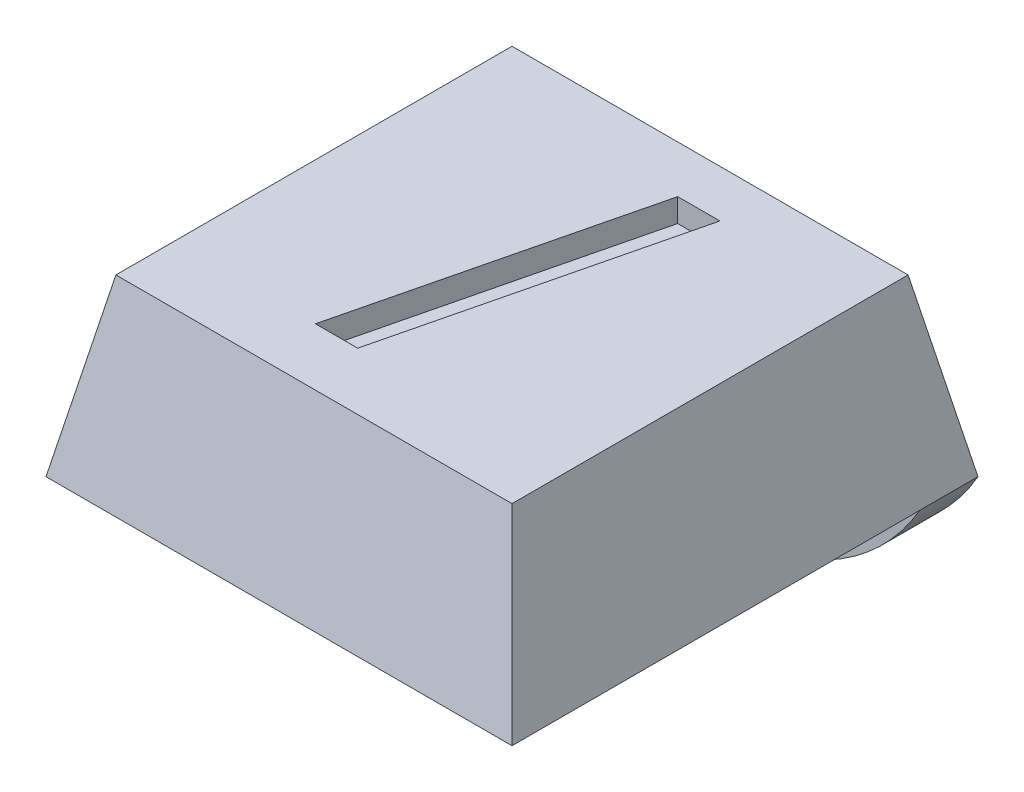
SolidWorks part; units mm, degrees
ref_plane "Front Plane" through (0, 0, 0) normal (0, 0, 1) x (1, 0, 0)
ref_plane "Top Plane" through (0, 0, 0) normal (0, 1, 0) x (1, 0, 0)
ref_plane "Right Plane" through (0, 0, 0) normal (1, 0, 0) x (0, 0, -1)
sketch "Sketch1" plane through (0, 0, 0) normal (0, 1, 0) x (1, 0, 0)
  line L1 (0, 0) -> (8, 0)
  line L2 (0, 0) -> (0, 8)
  line L3 (0, 8) -> (8, 8)
  line L4 (8, 0) -> (8, 8)
  dimension "D1" = 8
  dimension "D2" = 8
extrude "Boss-Extrude1" add sketch "Sketch1" along normal blind 3
sketch "Sketch2" plane through (0, 0, 0) normal (0, 0, 1) x (1, 0, 0)
  line L0 (0, 0) -> (0.6, 3)
  line L1 (0, 3) -> (8, 3) construction
  line L2 (0.6, 3) -> (0, 3)
  line L3 (0, 3) -> (0, 0)
  line L4 (8, 0) -> (7.4, 3)
  line L5 (7.4, 3) -> (8, 3)
  line L6 (8, 3) -> (8, 0)
  dimension "D1" = 0.6
  dimension "D2" = 0.6
extrude "Cut-Extrude1" cut sketch "Sketch2" against normal through all both and the other way through all
sketch "Sketch3" plane through (0, 0, 0) normal (1, 0, 0) x (0, 0, -1)
  line L0 (0, 0) -> (0.6, 3)
  line L1 (8, 3) -> (0, 3) construction
  line L2 (0.6, 3) -> (0, 3)
  line L3 (0, 3) -> (0, 0)
  line L4 (8, 3) -> (7.4, 3)
  line L5 (7.4, 3) -> (8, 0)
  line L6 (8, 3) -> (8, 0)
  dimension "D1" = 0.6
  dimension "D2" = 0.6
extrude "Cut-Extrude2" cut sketch "Sketch3" along normal blind 11
sketch "Sketch4" plane through (0, 0, 0) normal (0, -1, 0) x (1, 0, 0)
  line L0 (8, 0) -> (8, -8) construction
  line L3 (0, 0) -> (8, 0) construction
  circle A0 centre (4, -3.75) radius 1.75
  dimension "D1" = 3.5
  dimension "D2" = 4
  dimension "D3" = 3.75
extrude "Cut-Extrude3" cut sketch "Sketch4" against normal blind 0.4
sketch "Sketch5" plane through (0, 0, 0) normal (0, -1, 0) x (1, 0, 0)
  line L0 (8, 0) -> (8, -8) construction
  line L1 (0, -8) -> (8, -8)
  line L2 (0, -8) -> (0, -7)
  line L3 (0, -7) -> (8, -7)
  line L4 (8, -8) -> (8, -7)
  dimension "D1" = 1
extrude "Boss-Extrude2" add sketch "Sketch5" along normal blind 2
fillet "Fillet1" radius 4 2 edges at (8, -2, -7.5) (0, -2, -7.5)
sketch "Sketch6" plane through (0, 3, 0) normal (0, 1, 0) x (1, 0, 0)
  text T0 "/" font "Arial" height 5
extrude "Cut-Extrude4" cut sketch "Sketch6" against normal blind 0.4
